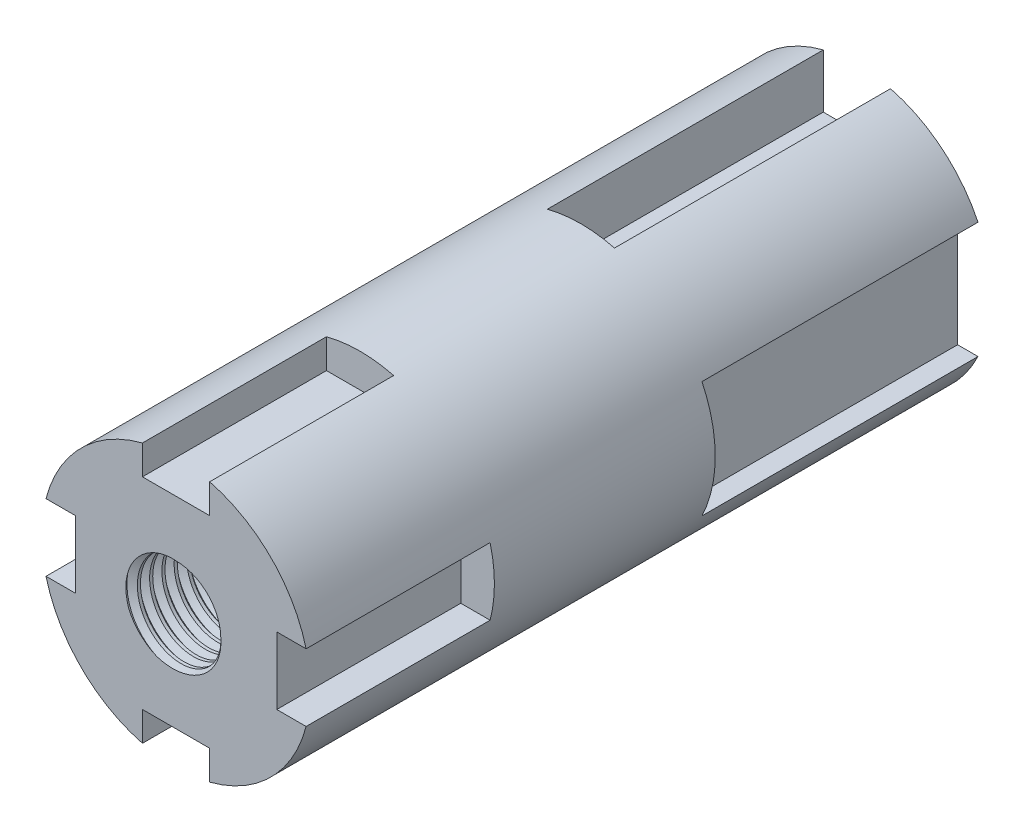
SolidWorks part; units mm, degrees
ref_plane "Front Plane" through (0, 0, 0) normal (0, 0, 1) x (1, 0, 0)
ref_plane "Top Plane" through (0, 0, 0) normal (0, 1, 0) x (1, 0, 0)
ref_plane "Right Plane" through (0, 0, 0) normal (1, 0, 0) x (0, 0, -1)
sketch "Sketch3" plane through (0, 0, 0) normal (0, 0, 1) x (1, 0, 0)
  circle A0 centre (0, 0) radius 5.475
  dimension "D1" = 10.95
extrude "Boss-Extrude2" add sketch "Sketch3" along normal blind 27.75
sketch "Sketch6" plane through (0, 0, 27.75) normal (0, 0, 1) x (1, 0, 0)
  line L10 (5.475, 1.37) -> (4.105, 1.37)
  line L11 (-1.37, 5.475) -> (1.37, 5.475)
  line L12 (-1.37, 5.475) -> (-1.37, 4.105)
  line L13 (-1.37, 4.105) -> (1.37, 4.105)
  line L14 (1.37, 5.475) -> (1.37, 4.105)
  line L15 (5.475, 1.37) -> (5.475, -1.37)
  line L16 (5.475, -1.37) -> (4.105, -1.37)
  line L17 (4.105, 1.37) -> (4.105, -1.37)
  line L18 (1.37, -5.475) -> (1.37, -4.105)
  line L19 (1.37, -5.475) -> (-1.37, -5.475)
  line L20 (-1.37, -5.475) -> (-1.37, -4.105)
  line L21 (1.37, -4.105) -> (-1.37, -4.105)
  line L22 (-5.475, -1.37) -> (-4.105, -1.37)
  line L23 (-5.475, -1.37) -> (-5.475, 1.37)
  line L24 (-5.475, 1.37) -> (-4.105, 1.37)
  line L25 (-4.105, -1.37) -> (-4.105, 1.37)
  circle A2 centre (0, 0) radius 5.475 construction
  point P4 (0, 5.475)
  point P23 (0, 0)
  dimension "D1" = 2.74
  dimension "D2" = 1.37
  dimension "D3" = 4
extrude "Cut-Extrude1" cut sketch "Sketch6" against normal blind 7.5
sketch "Sketch4" plane through (0, 0, 0) normal (0, 0, -1) x (-1, 0, 0)
  line L5 (-1.37, 3.105) -> (1.37, 3.105)
  line L6 (-1.37, 3.105) -> (-1.37, 5.475)
  line L7 (-1.37, 5.475) -> (1.37, 5.475)
  line L8 (1.37, 3.105) -> (1.37, 5.475)
  line L9 (-4.105, -2.37) -> (-5.475, -2.37)
  line L10 (-4.105, -2.37) -> (-4.105, 2.37)
  line L11 (-4.105, 2.37) -> (-5.475, 2.37)
  line L12 (-5.475, -2.37) -> (-5.475, 2.37)
  line L13 (-4.105, -2.37) -> (-5.475, 2.37) construction
  line L14 (-4.105, 2.37) -> (-5.475, -2.37) construction
  line L15 (4.105, -2.37) -> (5.475, -2.37)
  line L16 (4.105, -2.37) -> (4.105, 2.37)
  line L17 (4.105, 2.37) -> (5.475, 2.37)
  line L18 (5.475, -2.37) -> (5.475, 2.37)
  line L19 (4.105, -2.37) -> (5.475, 2.37) construction
  line L20 (4.105, 2.37) -> (5.475, -2.37) construction
  circle A2 centre (0, 0) radius 5.475 construction
  point P4 (0, 5.475)
  point P6 (-4.79, 0)
  point P13 (4.79, 0)
  dimension "D1" = 2.37
  dimension "D2" = 2.74
  dimension "D3" = 1.37
  dimension "D4" = 4.74
extrude "Cut-Extrude2" cut sketch "Sketch4" against normal blind 11.25
sketch "Sketch7" plane through (0, 0, 0) normal (0, 0, -1) x (-1, 0, 0)
  circle A0 centre (0, 0) radius 1.825
  dimension "D1" = 3.65
extrude "Cut-Extrude3" cut sketch "Sketch7" against normal blind 5
sketch "Sketch8" plane through (0, 0, 27.75) normal (0, 0, 1) x (1, 0, 0)
  circle A0 centre (0, 0) radius 1.825
  dimension "D1" = 3.65
extrude "Cut-Extrude4" cut sketch "Sketch8" against normal blind 5
thread "Thread1" pitch 0.5 method cut profile "Thread Profile1" start angle 0, offset 0, length 10, pitch 0.5, diameter 3.65
ref_plane "Plane1" through (-1.825, 0, 5) normal (0, -1, 0) x (-1, 0, 0)
sketch "Thread Profile1" plane through (-1.825, 0, 5) normal (0, -1, 0) x (-1, 0, 0)
  line L0 (0, 0) -> (0, 0.5) construction
  line L1 (0, 0) -> (0.2706, 0.1562)
  line L2 (0.2706, 0.1562) -> (0.2706, 0.2187)
  line L3 (0.2706, 0.2187) -> (0, 0.375)
  line L4 (0.2706, 0.1875) -> (0, 0.1875) construction
  line L11 (0, 0) -> (0, 0.375)
  point P2 (0, 0)
  dimension "Pitch" = 0.5
  dimension "Profile_Angle" = 60
  dimension "Profile_Land" = 0.0625
  dimension "Profile_Height" = 0.2706
thread "Thread2" pitch 0.5 method cut profile "Thread Profile2" start angle 0, offset 0, length 10, pitch 0.5, diameter 3.65
ref_plane "Plane2" through (1.825, 0, 22.75) normal (0, -1, 0) x (1, 0, 0)
sketch "Thread Profile2" plane through (1.825, 0, 22.75) normal (0, -1, 0) x (1, 0, 0)
  line L0 (0, 0) -> (0, 0.5) construction
  line L1 (0, 0) -> (0.2706, 0.1562)
  line L2 (0.2706, 0.1562) -> (0.2706, 0.2187)
  line L3 (0.2706, 0.2187) -> (0, 0.375)
  line L4 (0.2706, 0.1875) -> (0, 0.1875) construction
  line L11 (0, 0) -> (0, 0.375)
  point P2 (0, 0)
  dimension "Pitch" = 0.5
  dimension "Profile_Angle" = 60
  dimension "Profile_Land" = 0.0625
  dimension "Profile_Height" = 0.2706
equation "\"pin_diameter\"=10.95"
equation "\"pin_length\"=27.75"
equation "\"key_width\"=2.74"
equation "\"key_length\"=1.37"
equation "\"key_length_with_hump\"=2.37"
equation "\"key_width_with_offset\"=4.74"
equation "\"key_thickness\"=11.25"
equation "\"screw_diameter\"=3.65"
equation "\"D1@Sketch3\"=\"pin_diameter\""
equation "\"D1@Boss-Extrude2\"=\"pin_length\""
equation "\"D1@Sketch6\"=\"key_width\""
equation "\"D2@Sketch6\"=\"key_length\""
equation "\"D2@Sketch4\"=\"key_width\""
equation "\"D1@Sketch4\"=\"key_length_with_hump\""
equation "\"D4@Sketch4\"=\"key_width_with_offset\""
equation "\"D3@Sketch4\"=\"key_length\""
equation "\"D1@Cut-Extrude2\"=\"key_thickness\""
equation "\"D1@Sketch7\"=\"screw_diameter\""
equation "\"D1@Sketch8\"=\"screw_diameter\""
